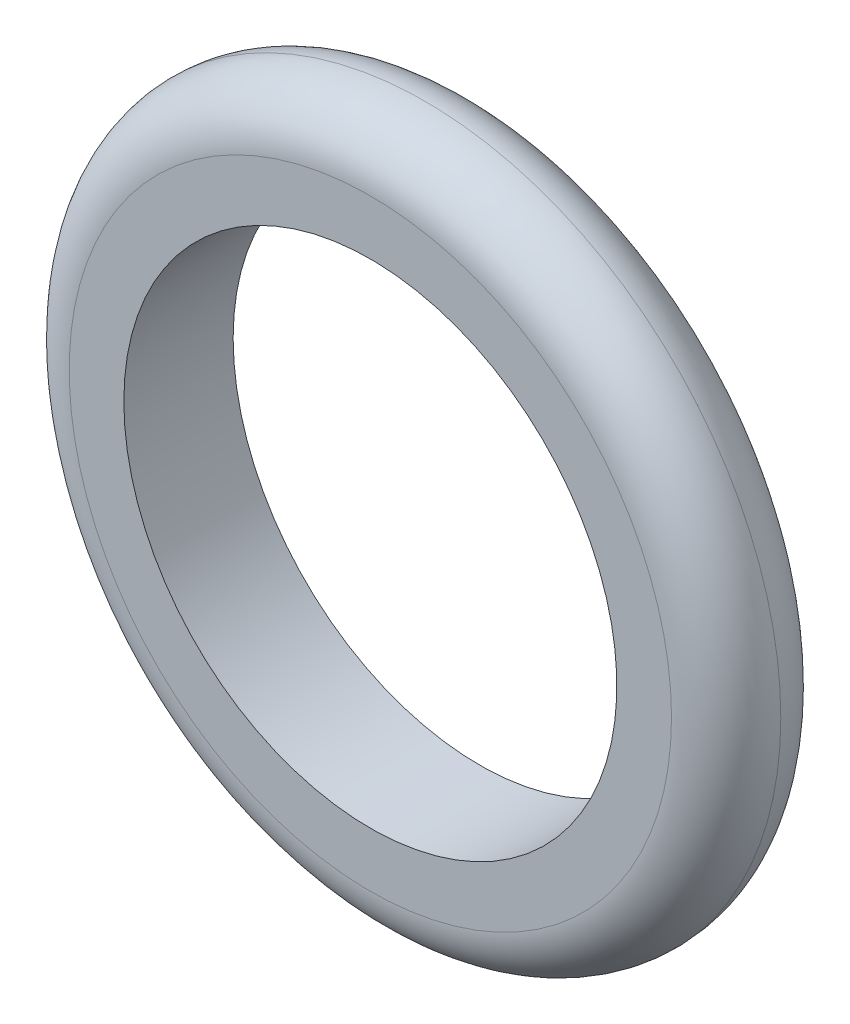
SolidWorks part; units mm, degrees
ref_plane "Płaszczyzna przednia" through (0, 0, 0) normal (0, 0, 1) x (1, 0, 0)
ref_plane "Płaszczyzna górna" through (0, 0, 0) normal (0, 1, 0) x (1, 0, 0)
ref_plane "Płaszczyzna prawa" through (0, 0, 0) normal (1, 0, 0) x (0, 0, -1)
sketch "Szkic1" plane through (0, 0, 0) normal (0, 0, 1) x (1, 0, 0)
  circle A0 centre (0, 0) radius 203
  circle A1 centre (0, 0) radius 293
  dimension "D1" = 406
  dimension "D2" = 586
extrude "Dodanie-wyciągnięcie1" add sketch "Szkic1" along normal blind 90
fillet "Zaokrąglenie1" radius 45 2 edges at (293, 0, 0) (293, 0, 90)
